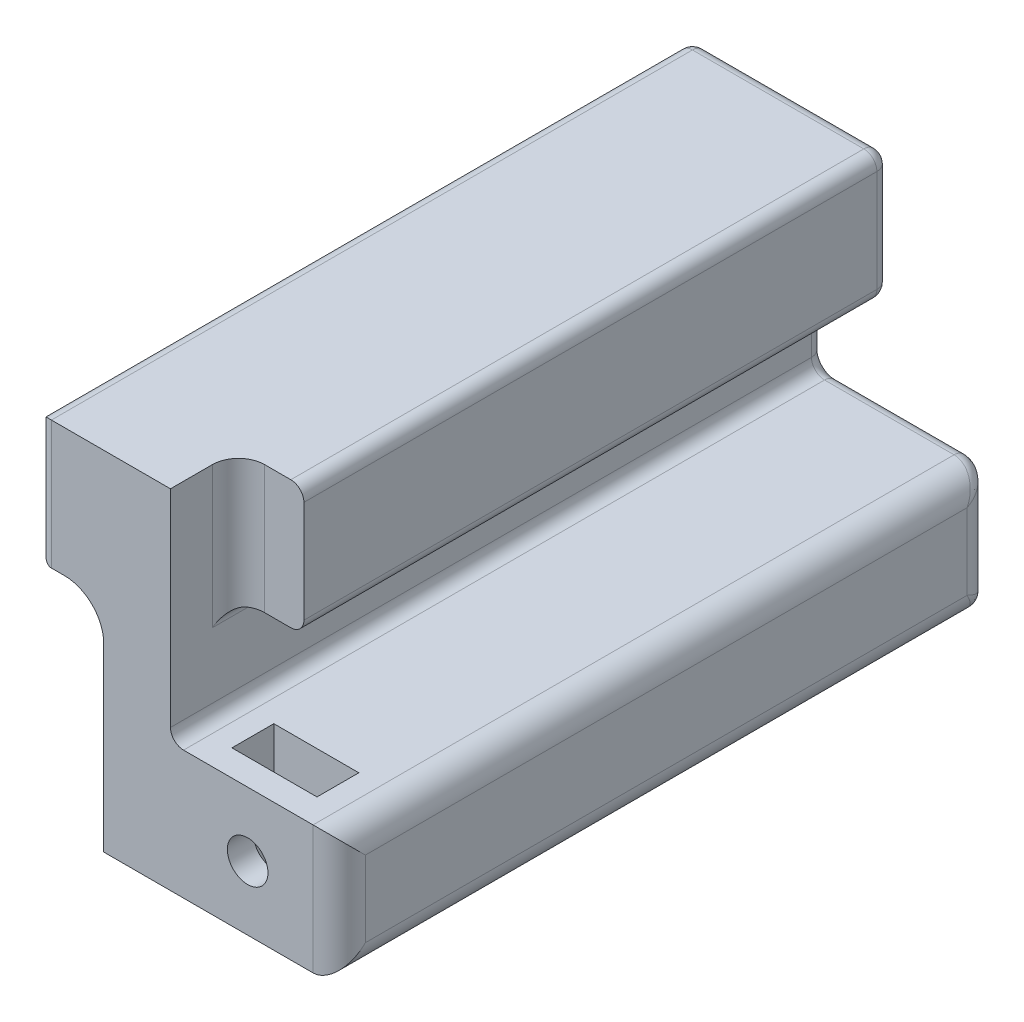
SolidWorks part; units mm, degrees
ref_plane "Front Plane" through (0, 0, 0) normal (0, 0, 1) x (1, 0, 0)
ref_plane "Top Plane" through (0, 0, 0) normal (0, 1, 0) x (1, 0, 0)
ref_plane "Right Plane" through (0, 0, 0) normal (1, 0, 0) x (0, 0, -1)
sketch "Sketch1" plane through (0, 0, 0) normal (0, 1, 0) x (1, 0, 0)
  line L1 (9, 25) -> (-9, 25)
  line L2 (9, 25) -> (9, -25)
  line L3 (9, -25) -> (-9, -25)
  line L4 (-9, 25) -> (-9, -25)
  line L5 (9, 25) -> (-9, -25) construction
  line L6 (9, -25) -> (-9, 25) construction
  point P0 (0, 0)
  dimension "D1" = 18
  dimension "D2" = 50
extrude "Boss-Extrude1" add sketch "Sketch1" along normal blind 9.8
sketch "Sketch2" plane through (0, 9.8, 0) normal (0, 1, 0) x (1, 0, 0)
  line L1 (-9, 25) -> (-3.9, 25)
  line L2 (-9, 25) -> (-9, -25)
  line L3 (-9, -25) -> (-3.9, -25)
  line L4 (-3.9, 25) -> (-3.9, -25)
  line L5 (-9, -25) -> (9, -25) construction
  dimension "D1" = 5.1
extrude "Boss-Extrude2" add sketch "Sketch2" along normal blind 7
fillet "Fillet1" radius 2 4 edges at (9, 4.9, 25) (9, 9.8, 0) (9, 4.9, -25) (9, 0, 0)
fillet "Fillet2" radius 1 1 edges at (-3.9, 9.8, 0)
sketch "Sketch3" plane through (0, 9.8, 0) normal (0, 1, 0) x (1, 0, 0)
  line L0 (-2.9, -25) -> (7, -25) construction
  line L1 (5.3, -19.8) -> (-1.2, -19.8)
  line L2 (5.3, -19.8) -> (5.3, -23)
  line L3 (5.3, -23) -> (-1.2, -23)
  line L4 (-1.2, -19.8) -> (-1.2, -23)
  line L5 (5.3, -19.8) -> (-1.2, -23) construction
  line L6 (5.3, -23) -> (-1.2, -19.8) construction
  point P0 (2.05, -21.4)
  point P8 (2.05, -25)
  dimension "D1" = 6.5
  dimension "D2" = 3.2
  dimension "D3" = 2
extrude "Cut-Extrude1" cut sketch "Sketch3" against normal blind 9
sketch "Sketch4" plane through (0, 0, 25) normal (0, 0, 1) x (1, 0, 0)
  line L1 (-9, 0) -> (7, 0) construction
  circle A0 centre (2, 4.9) radius 1.55
  dimension "D2" = 3.1
  dimension "D1" = 4.9
extrude "Cut-Extrude2" cut sketch "Sketch4" against normal blind 21.2
sketch "Sketch5" plane through (0, 16.8, 0) normal (0, 1, 0) x (1, 0, 0)
  line L1 (-14, 25) -> (1.1, 25)
  line L2 (-14, 25) -> (-14, -25)
  line L3 (-14, -25) -> (1.1, -25)
  line L4 (1.1, 25) -> (1.1, -25)
  line L5 (-3.9, 25) -> (-9, 25) construction
  line L6 (-9, -25) -> (-3.9, -25) construction
  line L7 (-3.9, -25) -> (-3.9, 25) construction
  line L8 (-9, 25) -> (-9, -25) construction
  dimension "D1" = 5
  dimension "D2" = 5
extrude "Boss-Extrude3" add sketch "Sketch5" along normal blind 9.8
fillet "Fillet3" radius 3 1 edges at (-9, 16.8, 0)
fillet "Fillet4" radius 1 20 edges at (8.4142, 0.5858, -24.4142) (8.4142, 9.2142, -24.4142) (-14, 26.6, 0) (-14, 21.7, 25) (-14, 16.8, 0) (1.1, 21.7, 25) (1.1, 26.6, 0) (1.1, 16.8, 0) (-3.6071, 10.0929, -25) (-3.9, 13.8, -25) (-1.4, 16.8, -25) (1.1, 21.7, -25) (-6.45, 26.6, -25) (-14, 21.7, -25) (-13, 16.8, -25) (-9.8787, 15.9213, -25) (-9, 6.9, -25) (-1, 0, -25) (2.05, 9.8, -25) (-3.9, 16.8, 0)
sketch "Sketch6" plane through (0, 26.6, 0) normal (0, 1, 0) x (1, 0, 0)
  line L0 (1.1, 24) -> (1.1, -24) construction
  line L1 (1.1, -25) -> (-3.9, -25)
  line L2 (1.1, -25) -> (1.1, -19.8)
  line L3 (1.1, -19.8) -> (-3.9, -19.8)
  line L4 (-3.9, -25) -> (-3.9, -19.8)
  line L5 (5.3, -19.8) -> (-1.2, -19.8) construction
  dimension "D1" = 0
  dimension "D2" = 5
  dimension "D3" = 0
extrude "Cut-Extrude3" cut sketch "Sketch6" against normal blind 12
fillet "Fillet5" radius 2 1 edges at (-3.9, 21.2, 19.8)
sketch "Sketch7" plane through (0, 0, -25) normal (0, 0, -1) x (-1, 0, 0)
  line L0 (13, 17.8) -> (13, 25.6) construction
  line L1 (13, 25.6) -> (-0.1, 25.6) construction
  circle A0 centre (6.45, 21.7) radius 4.1
  point P4 (13, 21.7)
  point P7 (6.45, 25.6)
  dimension "D1" = 8.2
extrude "Cut-Extrude4" cut sketch "Sketch7" against normal blind 2.2
